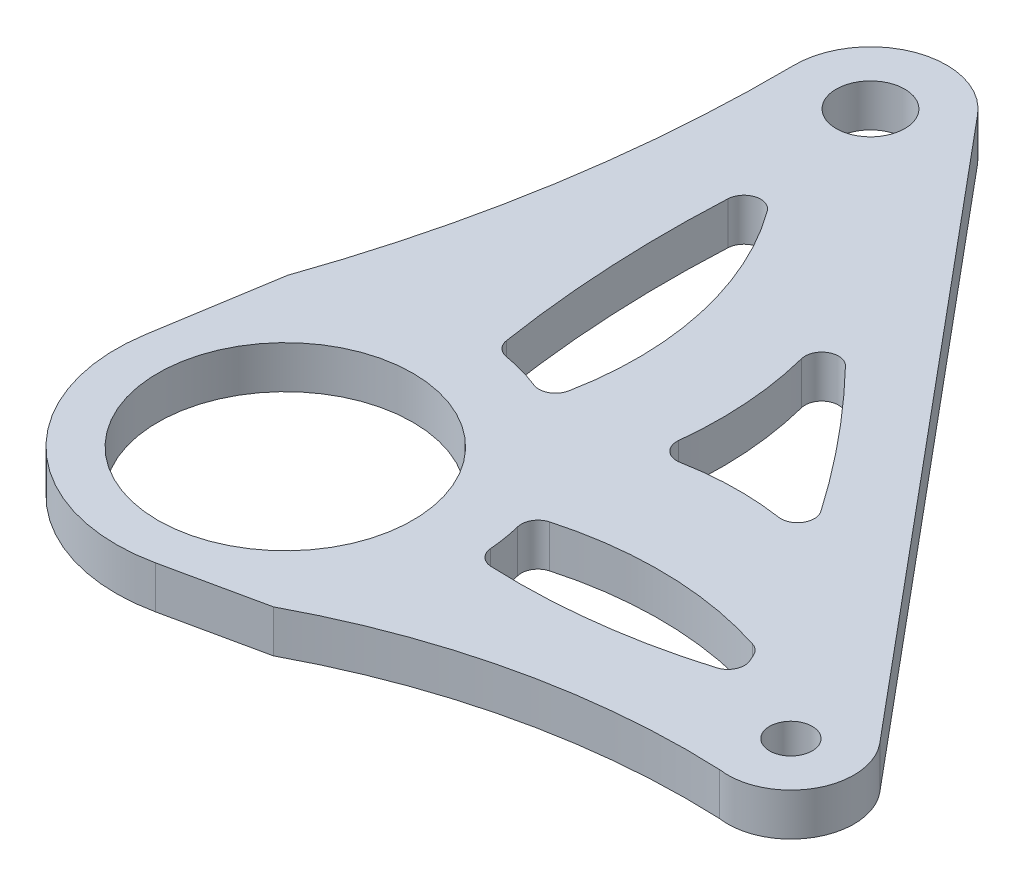
SolidWorks part; units mm, degrees
ref_plane "Front Plane" through (0, 0, 0) normal (0, 0, 1) x (1, 0, 0)
ref_plane "Top Plane" through (0, 0, 0) normal (0, 1, 0) x (1, 0, 0)
ref_plane "Right Plane" through (0, 0, 0) normal (1, 0, 0) x (0, 0, -1)
sketch "Sketch1" plane through (0, 0, 0) normal (0, 1, 0) x (1, 0, 0)
  line L0 (0, 70) -> (0, 0) construction
  line L1 (-8.9838, 71.4495) -> (-19.9915, 3.2255)
  line L2 (6.9846, 75.8332) -> (66.2749, 4.8396)
  line L3 (4.2522, -19.7985) -> (62.0654, -7.3817)
  circle A0 centre (0, 0) radius 15.25
  circle A1 centre (0, 70) radius 4.1
  circle A2 centre (60.48, 0) radius 2.55
  circle A3 centre (0, 70) radius 9.1
  circle A4 centre (0, 0) radius 20.25
  circle A5 centre (60.48, 0) radius 7.55
  dimension "D1" = 8.2
  dimension "D2" = 30.5
  dimension "D3" = 5.1
  dimension "D5" = 60.48
  dimension "D4" = 70
  dimension "D6" = 5
extrude "Boss-Extrude1" add sketch "Sketch1" along normal blind 5.08 contours A1 A3 | A3 L0 A4 L3 A5 L2 | A4 A0 | L0 A3 L1 A4 | A5 A2 region at (-6.7323, 0, -64.2669) region at (26.65, 0, -22.8875) region at (-7.7791, 0, -37.8765) region at (13.9139, 0, -13.9139) region at (67.3769, 0, -2.5012)
sketch "Sketch3" plane through (0, 5.08, 0) normal (0, 1, 0) x (1, 0, 0)
  line L23 (6.9846, 75.8332) -> (66.2749, 4.8396) construction
  line L24 (6.9846, 75.8332) -> (66.2749, 4.8396)
  circle A29 centre (0, 70) radius 9.1
  circle A30 centre (0, 0) radius 22.8895
  circle A31 centre (60.48, 0) radius 7.55
  arc A32 (1.1422, 57.1696) -> (10.6054, 20.2843) centre (-27.1739, 30.2482) cw
  arc A33 (-9.1, 70) -> (-21.0882, 8.9004) centre (-161.5637, 68.1886) cw
  arc A34 (11.8332, -19.5934) -> (59.4057, -7.4732) centre (55.6461, -92.1387) cw
  arc A35 (62.0654, -7.3817) -> (66.2749, 4.8396) centre (60.48, 0) ccw construction
  arc A37 (6.9846, 75.8332) -> (-8.9838, 71.4495) centre (0, 70) ccw construction
  arc A38 (1.5413, 61.0315) -> (2.4742, 22.7554) centre (136.1757, 45.1634) ccw
  arc A39 (1.5413, 61.0315) -> (53.4113, -2.6526) centre (-67.7138, -48.3419) cw
  arc A40 (22.8895, 0) -> (54.8847, 5.069) centre (27.9061, 71.8454) ccw
  arc A41 (18.9551, 47.8211) -> (19.6643, 11.7151) centre (-21.3828, 28.9688) cw
  arc A42 (14.268, 17.8984) -> (41.5062, 21.1549) centre (31.6533, -11.9755) cw
  arc A43 (21.6511, 7.4268) -> (49.2082, 7.2283) centre (35.1367, -33.3303) cw
  point P32 (22.8895, 0)
  point P44 (20.25, 0)
  point P45 (18.685, 8.9199)
  point P46 (0, 0)
  point P47 (18.685, 6.3554)
  point P48 (49.2082, 7.2283)
  line M15 (-8.9838, 71.4495) -> (-19.9915, 3.2255)
  line M17 (4.2522, -19.7985) -> (62.0654, -7.3817)
extrude "Cut-Extrude1" cut sketch "Sketch3" against normal through all contours A33 A29 A30 M15 | A32 A38 A30 | A41 A42 A39 | A43 A40 A39 | A34 A30 A31 M17 region at (-12.4338, 5.08, -44.1327) region at (38.2558, 5.08, 11.1719) region at (35.1339, 5.08, -4.7843) region at (5.7836, 5.08, -36.6354) region at (28.6759, 5.08, -30.5636)
sketch "Sketch2" plane through (0, 5.08, 0) normal (0, 1, 0) x (1, 0, 0)
  circle A7 centre (0, 0) radius 15.25
  circle A8 centre (0, 0) radius 20.25
  arc A9 (59.4057, -7.4732) -> (15.872, -17.3029) centre (55.6461, -92.1387) ccw construction
  arc A10 (-17.6263, 17.8848) -> (-9.0977, 69.796) centre (-161.5637, 68.1886) ccw construction
  arc A11 (59.4057, -7.4732) -> (15.872, -17.3029) centre (55.6461, -92.1387) ccw
  arc A12 (-17.6263, 17.8848) -> (-9.0977, 69.796) centre (-161.5637, 68.1886) ccw
extrude "Boss-Extrude2" add sketch "Sketch2" along normal blind 9 rebuild error yes
mirror "Mirror1" rebuild error yes
ref_plane "Plane1" through (0, 14.08, 0) normal (0, -1, 0) x (-1, 0, 0)
ref_axis "Axis1" through (60.48, 5.08, 0) along (0, -1, 0)
ref_point "Pushrod Pt"
sketch "Sketch4" plane through (0, 14.08, 0) normal (0, -1, 0) x (-1, 0, 0)
  line L0 (0, 70) -> (0, 0)
  line L1 (0, 0) -> (-60.48, 0)
  line L2 (-60.48, 0) -> (0, 70)
fillet "Fillet1" radius 2 10 edges at (50.8713, 2.54, -3.5847) (22.8895, 2.54, 0) (21.6511, 2.54, -7.4268) (49.2082, 2.54, -7.2283) (41.5062, 2.54, -21.1549) (18.9551, 2.54, -47.8211) (22.4866, 2.54, -21.3513) (10.6054, 2.54, -20.2843) (2.4742, 2.54, -22.7554) (1.1422, 2.54, -57.1696)
